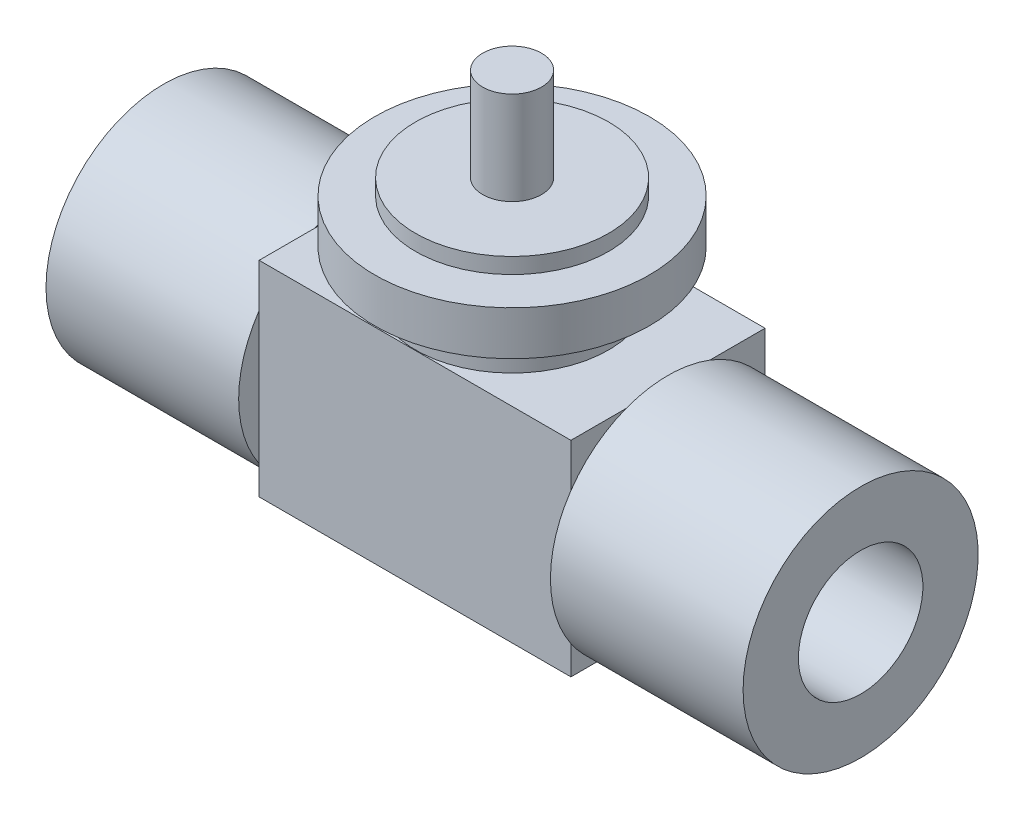
SolidWorks part; units mm, degrees
ref_plane "Front Plane" through (0, 0, 0) normal (0, 0, 1) x (1, 0, 0)
ref_plane "Top Plane" through (0, 0, 0) normal (0, 1, 0) x (1, 0, 0)
ref_plane "Right Plane" through (0, 0, 0) normal (1, 0, 0) x (0, 0, -1)
sketch "Body Sketch" plane through (0, 0, 0) normal (0, 0, 1) x (1, 0, 0)
  line L0 (-15.9, -9.7) -> (15.9, -9.7)
  line L1 (15.9, -9.7) -> (15.9, 11.2)
  line L2 (15.9, 11.2) -> (-15.9, 11.2)
  line L3 (-15.9, 11.2) -> (-15.9, -9.7)
extrude "Body" add sketch "Body Sketch" along normal mid plane 19.8
ref_axis "Engine Axis" through (39.105, 0, 0) along (-1, 0, 0)
ref_axis "Stem Axis" through (0, -14.1374, 0) along (0, 1, 0)
sketch "Nut +X Sketch" plane through (0, 0, 0) normal (0, 0, 1) x (1, 0, 0)
  line L0 (-1000, 0) -> (1000, 0) construction
  line L1 (15.9, 0) -> (35.55, 0)
  line L2 (35.55, 0) -> (35.55, 11.988)
  line L3 (35.55, 11.988) -> (15.9, 11.988)
  line L4 (15.9, 11.988) -> (15.9, 0)
revolve "Nut +X" add sketch "Nut +X Sketch" angle 360 about L0
sketch "Nut -X Sketch" plane through (0, 0, 0) normal (0, 0, 1) x (1, 0, 0)
  line L0 (-1000, 0) -> (1000, 0) construction
  line L1 (-35.55, 0) -> (-15.9, 0)
  line L2 (-15.9, 0) -> (-15.9, 11.988)
  line L3 (-15.9, 11.988) -> (-35.55, 11.988)
  line L4 (-35.55, 11.988) -> (-35.55, 0)
revolve "Nut -X" add sketch "Nut -X Sketch" angle 360 about L0
sketch "Socket +X Sketch" plane through (0, 0, 0) normal (0, 0, 1) x (1, 0, 0)
  line L0 (-1000, 0) -> (1000, 0) construction
  line L1 (12.65, 0) -> (36.55, 0)
  line L2 (36.55, 0) -> (36.55, 6.35)
  line L3 (36.55, 6.35) -> (12.65, 6.35)
  line L4 (12.65, 6.35) -> (12.65, 0)
revolve "Socket +X" cut sketch "Socket +X Sketch" angle 360 about L0
sketch "Socket -X Sketch" plane through (0, 0, 0) normal (0, 0, 1) x (1, 0, 0)
  line L0 (-1000, 0) -> (1000, 0) construction
  line L1 (-36.55, 0) -> (-12.65, 0)
  line L2 (-12.65, 0) -> (-12.65, 6.35)
  line L3 (-12.65, 6.35) -> (-36.55, 6.35)
  line L4 (-36.55, 6.35) -> (-36.55, 0)
revolve "Socket -X" cut sketch "Socket -X Sketch" angle 360 about L0
sketch "Stem Sketch" plane through (0, 0, 0) normal (0, 0, 1) x (1, 0, 0)
  line L0 (0, -500) -> (0, 500) construction
  line L1 (0, 11.2) -> (9.85, 11.2)
  line L2 (9.85, 11.2) -> (9.85, 15.4)
  line L3 (9.85, 15.4) -> (14, 15.4)
  line L4 (14, 15.4) -> (14, 19.9)
  line L5 (14, 19.9) -> (9.85, 19.9)
  line L6 (9.85, 19.9) -> (9.85, 21.5)
  line L7 (9.85, 21.5) -> (3, 21.5)
  line L8 (3, 21.5) -> (3, 31)
  line L9 (3, 31) -> (0, 31)
  line L10 (0, 31) -> (0, 11.2)
revolve "Stem" add sketch "Stem Sketch" angle 360 about L0
